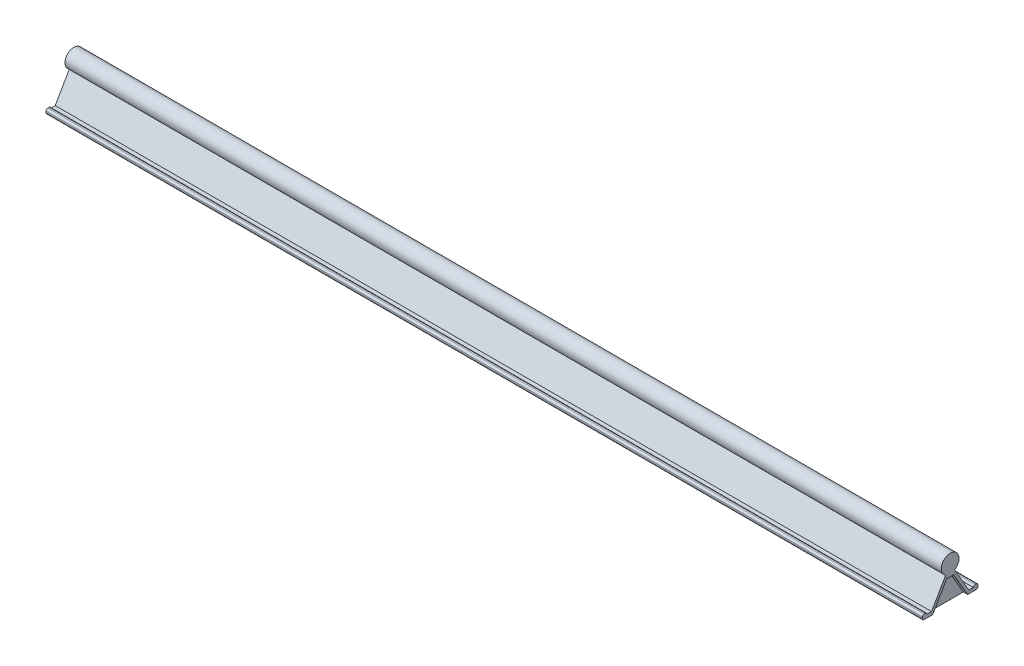
SolidWorks part; units mm, degrees
ref_plane "Front Plane" through (0, 0, 0) normal (0, 0, 1) x (1, 0, 0)
ref_plane "Top Plane" through (0, 0, 0) normal (0, 1, 0) x (1, 0, 0)
ref_plane "Right Plane" through (0, 0, 0) normal (1, 0, 0) x (0, 0, -1)
sketch "Sketch1" plane through (0, 0, 0) normal (1, 0, 0) x (0, 0, -1)
  line L0 (0, 0) -> (0, 40.64) construction
  line L1 (0, 50.8) -> (67.1648, 50.8) construction
  line L2 (1000, 30.48) -> (5.8659, 30.48) construction
  line L3 (-21.2638, 3.81) -> (-5.08, 31.8412)
  line L4 (5.08, 31.8412) -> (21.2638, 3.81)
  line L5 (-21.2638, 3.81) -> (-26.3438, 3.81)
  line L6 (-26.3438, 3.81) -> (-26.3438, 5.588)
  line L7 (-26.3438, 5.588) -> (-31.75, 5.588)
  line L8 (-31.75, 5.588) -> (-31.75, 0)
  line L9 (-31.75, 0) -> (31.75, 0)
  line L10 (31.75, 5.588) -> (31.75, 0)
  line L11 (26.3438, 5.588) -> (31.75, 5.588)
  line L12 (26.3438, 3.81) -> (26.3438, 5.588)
  line L13 (21.2638, 3.81) -> (26.3438, 3.81)
  line L14 (-5.8659, 30.48) -> (-18.71, 30.48) construction
  arc A0 (5.08, 31.8412) -> (-5.08, 31.8412) centre (0, 40.64) ccw
  point P18 (0, 0)
  dimension "D1" = 30.48
  dimension "D2" = 20.32
  dimension "D3" = 60
  dimension "D4" = 63.5
  dimension "D5" = 5.08
  dimension "D6" = 3.81
  dimension "D7" = 5.588
extrude "Boss-Extrude1" add sketch "Sketch1" along normal blind 1000
sketch "Sketch2" plane through (0, 0, 0) normal (-1, 0, 0) x (0, 0, 1)
  line L0 (18.2674, 3) -> (18.2674, 3)
  line L1 (18.2674, 3) -> (3.8087, 28.0432)
  line L2 (-3.8087, 28.0432) -> (-18.2674, 3)
  line L3 (-18.2674, 3) -> (-18.2674, 3)
  line L4 (-18.2674, 3) -> (-18.2674, 3)
  line L5 (-18.2674, 3) -> (-18.2674, 3)
  line L6 (-18.2674, 3) -> (-18.2674, 3)
  line L8 (18.2674, 3) -> (18.2674, 3)
  line L9 (18.2674, 3) -> (18.2674, 3)
  line L10 (18.2674, 3) -> (18.2674, 3)
  line L11 (26.3438, 3.81) -> (21.2638, 3.81)
  line L12 (21.2638, 3.81) -> (5.08, 31.8412)
  line L13 (-5.08, 31.8412) -> (-21.2638, 3.81)
  line L14 (-21.2638, 3.81) -> (-26.3438, 3.81)
  line L15 (-26.3438, 3.81) -> (-26.3438, 5.588)
  line L16 (-26.3438, 5.588) -> (-31.75, 5.588)
  line L17 (-31.75, 5.588) -> (-31.75, 0)
  line L18 (-31.75, 0) -> (31.75, 0)
  line L19 (31.75, 0) -> (31.75, 5.588)
  line L20 (31.75, 5.588) -> (26.3438, 5.588)
  line L21 (26.3438, 5.588) -> (26.3438, 3.81)
  line L22 (26.3438, 3.81) -> (21.2638, 3.81) construction
  line L23 (21.2638, 3.81) -> (5.08, 31.8412) construction
  line L24 (-5.08, 31.8412) -> (-21.2638, 3.81) construction
  line L25 (-21.2638, 3.81) -> (-26.3438, 3.81) construction
  line L26 (-26.3438, 3.81) -> (-26.3438, 5.588) construction
  line L27 (-26.3438, 5.588) -> (-31.75, 5.588) construction
  line L28 (-31.75, 5.588) -> (-31.75, 0) construction
  line L29 (-31.75, 0) -> (31.75, 0) construction
  line L30 (31.75, 0) -> (31.75, 5.588) construction
  line L31 (31.75, 5.588) -> (26.3438, 5.588) construction
  line L32 (26.3438, 5.588) -> (26.3438, 3.81) construction
  line L33 (18.2674, 3) -> (0.6525, 33.5098) construction
  line L34 (-0.6525, 33.5098) -> (-18.2674, 3) construction
  line L35 (-18.2674, 3) -> (-19.9994, 0)
  line L36 (18.2674, 3) -> (19.9994, 0)
  line L37 (19.9994, 0) -> (-19.9994, 0)
  line L39 (-18.2674, 3) -> (18.2674, 3) construction
  arc A1 (5.08, 31.8412) -> (-5.08, 31.8412) centre (0, 40.64) ccw
  arc A2 (5.08, 31.8412) -> (-5.08, 31.8412) centre (0, 40.64) ccw construction
  arc A3 (0.6525, 33.5098) -> (-0.6525, 33.5098) centre (0, 40.64) ccw construction
  arc A5 (-3.8087, 28.0432) -> (3.8087, 28.0432) centre (0, 40.64) ccw
  line M23 (-31.75, 0) -> (31.75, 0)
  dimension "D3" = 3
  dimension "D1" = 0
  dimension "D2" = 3
extrude "Cut-Extrude1" cut sketch "Sketch2" against normal blind 5 contours A5 L2 L35 L36 L1 M23 region at (0, 10.7698, 0)
ref_plane "Plane4" through (500, 0, 0) normal (-1, 0, 0) x (0, 0, 1)
mirror "Mirror1" about plane through (500, 0, 0) normal (-1, 0, 0) of "Cut-Extrude1"
fillet "Fillet1" radius 2 6 edges at (500, 0, 31.75) (500, 5.588, 26.3438) (500, 5.588, 31.75) (500, 0, -31.75) (500, 5.588, -31.75) (500, 5.588, -26.3438)
